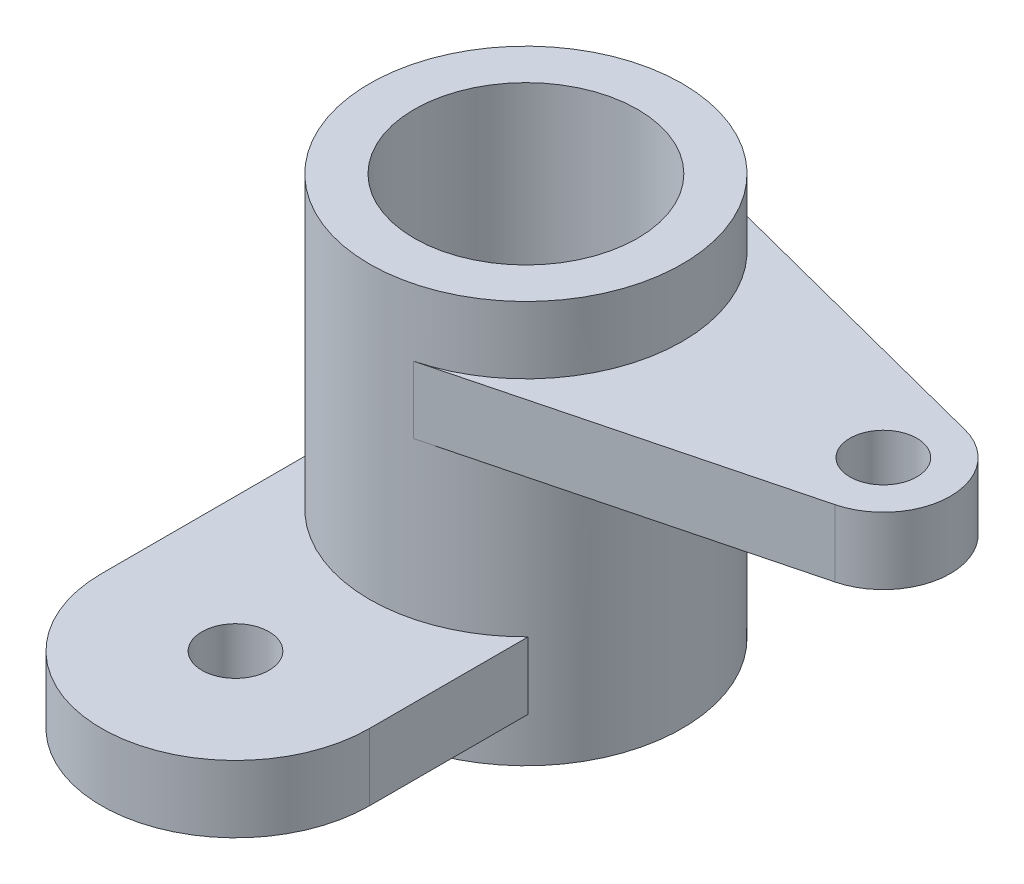
SolidWorks part; units mm, degrees
ref_plane "Front Plane" through (0, 0, 0) normal (0, 0, 1) x (1, 0, 0)
ref_plane "Top Plane" through (0, 0, 0) normal (0, 1, 0) x (1, 0, 0)
ref_plane "Right Plane" through (0, 0, 0) normal (1, 0, 0) x (0, 0, -1)
sketch "Sketch1" plane through (0, 0, 0) normal (0, 1, 0) x (1, 0, 0)
  line L0 (8.75, 33.8886) -> (83.75, 14.5237)
  line L1 (8.75, -33.8886) -> (83.75, -14.5237)
  line L2 (-35, 0) -> (-35, -60)
  line L3 (25, -60) -> (25, -24.4949)
  circle A0 centre (0, 0) radius 35
  circle A1 centre (0, 0) radius 25
  circle A2 centre (80, 0) radius 15
  circle A3 centre (80, 0) radius 7.5
  arc A4 (-35, -60) -> (25, -60) centre (-5, -60) ccw
  circle A5 centre (-5, -60) radius 7.5
  dimension "D1" = 70
  dimension "D2" = 50
  dimension "D3" = 30
  dimension "D4" = 15
  dimension "D6" = 60
  dimension "D8" = 15
  dimension "D5" = 80
  dimension "D7" = 60
extrude "Boss-Extrude1" add sketch "Sketch1" against normal blind 90 contours A0 A1 region at (26.8873, 0, -20.8268)
extrude "Boss-Extrude2" add sketch "Sketch1<3>" against normal blind 15 from offset 65 contours L2 A4 L3 L1 A0 A5 | A0 L1 L3 region at (-22.0954, 0, 28.5251) region at (21.0932, 0, 29.1879) offset against normal yes
sketch "Sketch1<3>" plane through (0, 0, 0) normal (0, 1, 0) x (1, 0, 0) same geometry as "Sketch1"
extrude "Boss-Extrude3" add sketch "Sketch1<4>" against normal blind 15 from offset 15 contours A0 L1 L3 | A2 L0 A0 L3 L1 | A2 A3 region at (48.3793, 0, -0.4187) region at (91.5231, 0, -8.9258) region at (21.0932, 0, 29.1879) offset against normal yes
sketch "Sketch1<4>" plane through (0, 0, 0) normal (0, 1, 0) x (1, 0, 0) same geometry as "Sketch1"
